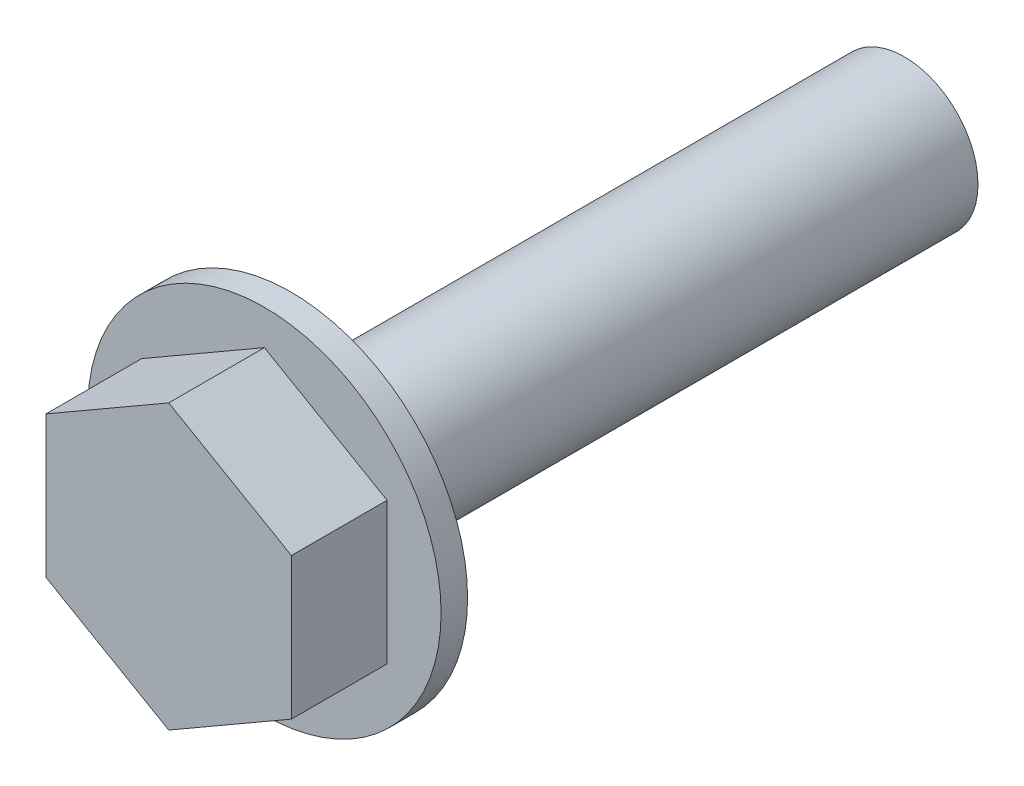
SolidWorks part; units mm, degrees
material "AISI Type 316L stainless steel"
ref_plane "Front Plane" through (0, 0, 0) normal (0, 0, 1) x (1, 0, 0)
ref_plane "Top Plane" through (0, 0, 0) normal (0, 1, 0) x (1, 0, 0)
ref_plane "Right Plane" through (0, 0, 0) normal (1, 0, 0) x (0, 0, -1)
sketch "Extrude sketch 1" plane through (0, 0, 0) normal (0, 0, 1) x (1, 0, 0)
  circle A0 centre (0, 0) radius 7.2
  dimension "D1" = 14.4
extrude "Extrude 1" add sketch "Extrude sketch 1" along normal blind 1.08 separate body
sketch "Extrude sketch 2" plane through (0, 0, 0) normal (0, 0, 1) x (1, 0, 0)
  line L0 (5, 2.8868) -> (0, 5.7735)
  line L1 (0, 5.7735) -> (-5, 2.8868)
  line L2 (-5, 2.8868) -> (-5, -2.8868)
  line L3 (-5, -2.8868) -> (0, -5.7735)
  line L4 (0, -5.7735) -> (5, -2.8868)
  line L5 (5, -2.8868) -> (5, 2.8868)
  dimension "D1" = 5
  dimension "D2" = 2.8868
extrude "Extrude 2" add sketch "Extrude sketch 2" along normal blind 3.9 from offset 1.08 separate body
sketch "Extrude sketch 3" plane through (0, 0, 0) normal (0, 0, 1) x (1, 0, 0)
  circle A0 centre (0, 0) radius 3
  dimension "D1" = 6
extrude "Extrude 3" add sketch "Extrude sketch 3" along normal blind 25.01 from offset 25 separate body offset against normal yes
combine bodies "Combine (weld / assembly of features)" operation type add bodies to combine 102 101 103
